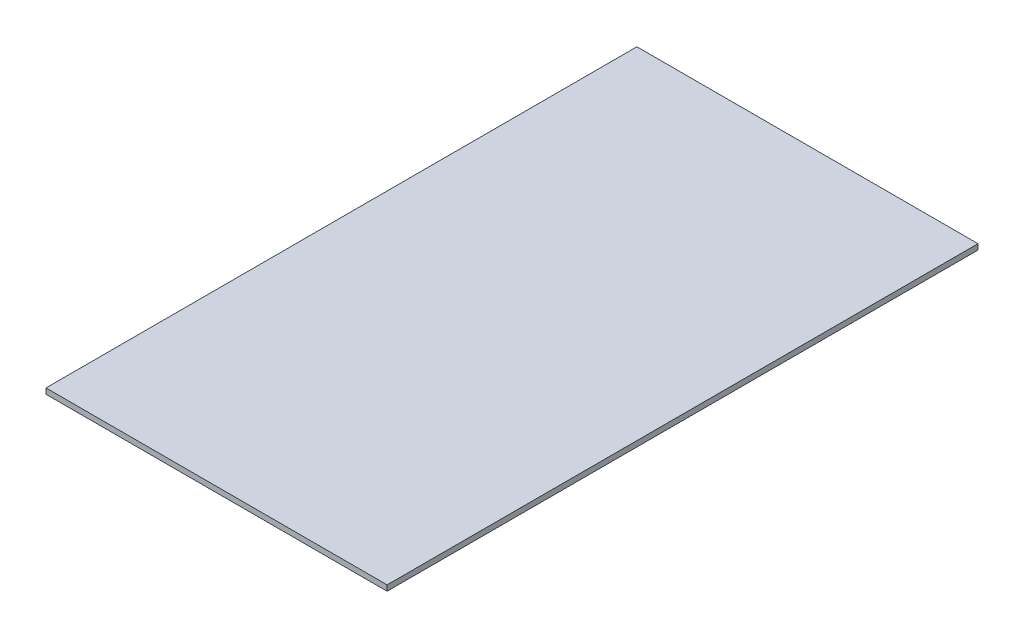
SolidWorks part; units mm, degrees
ref_plane "前视基准面" through (0, 0, 0) normal (0, 0, 1) x (1, 0, 0)
ref_plane "上视基准面" through (0, 0, 0) normal (0, 1, 0) x (1, 0, 0)
ref_plane "右视基准面" through (0, 0, 0) normal (1, 0, 0) x (0, 0, -1)
other "Configuration Table"
sketch "草图1" plane through (0, 0, 0) normal (0, 1, 0) x (1, 0, 0)
  line L1 (-92.53, 160.295) -> (92.53, 160.295)
  line L2 (-92.53, 160.295) -> (-92.53, -160.295)
  line L3 (-92.53, -160.295) -> (92.53, -160.295)
  line L4 (92.53, 160.295) -> (92.53, -160.295)
  line L5 (-92.53, 160.295) -> (92.53, -160.295) construction
  line L6 (-92.53, -160.295) -> (92.53, 160.295) construction
  point P0 (0, 0)
  dimension "D1" = 185.06
  dimension "D2" = 320.59
extrude "凸台-拉伸1" add sketch "草图1" along normal blind 3
